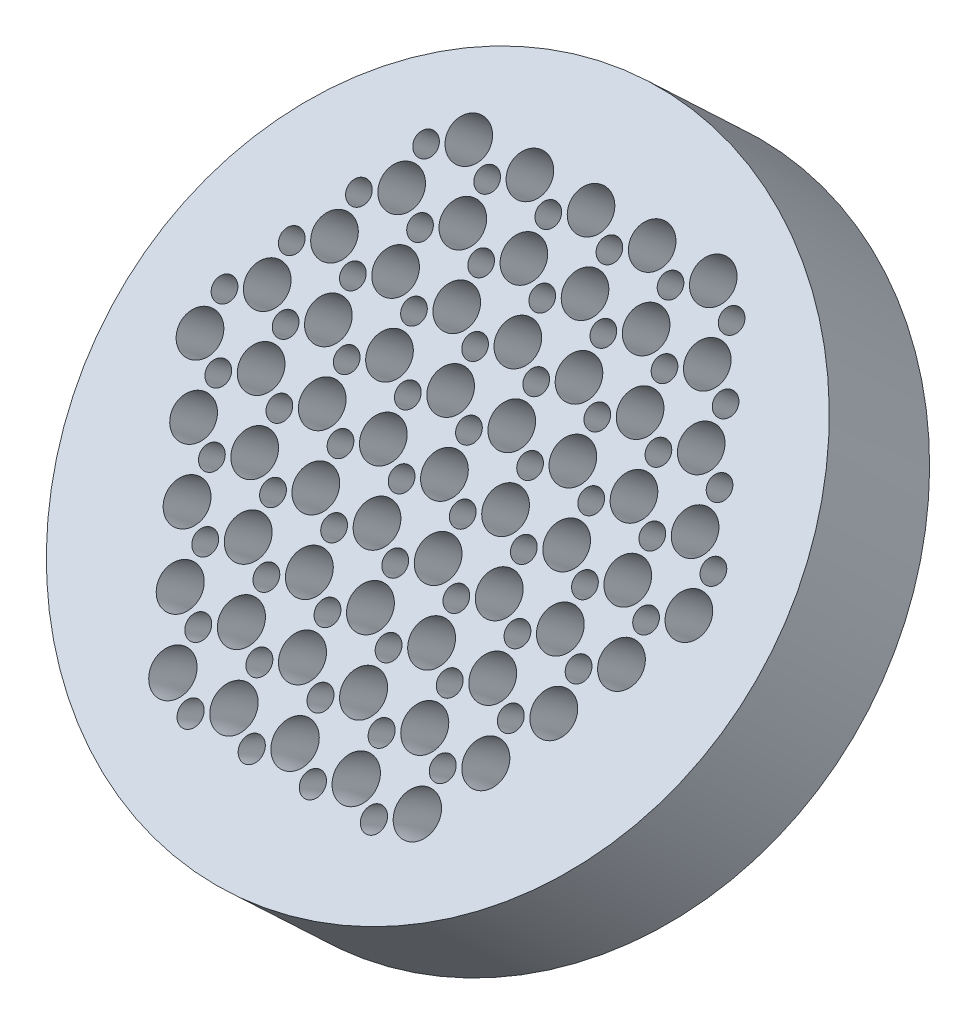
SolidWorks part; units mm, degrees
ref_plane "Спереди" through (0, 0, 0) normal (0, 0, 1) x (1, 0, 0)
ref_plane "Сверху" through (0, 0, 0) normal (0, 1, 0) x (1, 0, 0)
ref_plane "Справа" through (0, 0, 0) normal (1, 0, 0) x (0, 0, -1)
sketch "Sketch1" plane through (0, 0, 0) normal (0, 0, 1) x (1, 0, 0)
  line L0 (3.9, 6.755) -> (7.8, 0) construction
  line L2 (5.85, 10.1325) -> (11.7, 0) construction
  line L4 (7.8, 13.51) -> (15.6, 0) construction
  circle A61 centre (0, 0) radius 18.6468
  circle A131 centre (0, 0) radius 1.25
  circle A484 centre (3.9, 0) radius 1.25
  circle A485 centre (7.8, 0) radius 1.25
  circle A486 centre (11.7, 0) radius 1.25
  circle A487 centre (15.6, 0) radius 1.25
  circle A488 centre (1.95, -3.3775) radius 1.25
  circle A489 centre (3.9, -6.755) radius 1.25
  circle A490 centre (5.85, -10.1325) radius 1.25
  circle A491 centre (7.8, -13.51) radius 1.25
  circle A492 centre (-1.95, -3.3775) radius 1.25
  circle A493 centre (-3.9, -6.755) radius 1.25
  circle A494 centre (-5.85, -10.1325) radius 1.25
  circle A495 centre (-7.8, -13.51) radius 1.25
  circle A496 centre (-3.9, 0) radius 1.25
  circle A497 centre (-7.8, 0) radius 1.25
  circle A498 centre (-11.7, 0) radius 1.25
  circle A499 centre (-15.6, 0) radius 1.25
  circle A500 centre (-1.95, 3.3775) radius 1.25
  circle A501 centre (-3.9, 6.755) radius 1.25
  circle A502 centre (-5.85, 10.1325) radius 1.25
  circle A503 centre (-7.8, 13.51) radius 1.25
  circle A504 centre (1.95, 3.3775) radius 1.25
  circle A505 centre (3.9, 6.755) radius 1.25
  circle A506 centre (5.85, 10.1325) radius 1.25
  circle A507 centre (7.8, 13.51) radius 1.25
  circle A508 centre (5.85, 3.3775) radius 1.25
  circle A509 centre (7.8, 6.755) radius 1.25
  circle A510 centre (9.75, 3.3775) radius 1.25
  circle A511 centre (11.7, 6.755) radius 1.25
  circle A512 centre (9.7491, 10.1341) radius 1.25
  circle A513 centre (13.6509, 3.3759) radius 1.25
  circle A514 centre (5.85, -3.3791) radius 1.25
  circle A515 centre (9.75, -3.3791) radius 1.25
  circle A516 centre (7.8, -6.7566) radius 1.25
  circle A517 centre (11.7, -6.7566) radius 1.25
  circle A518 centre (9.7491, -10.1356) radius 1.25
  circle A519 centre (13.6509, -3.3775) radius 1.25
  circle A520 centre (-0.0013, -6.7573) radius 1.25
  circle A521 centre (1.9487, -10.1348) radius 1.25
  circle A522 centre (-1.9513, -10.1348) radius 1.25
  circle A523 centre (-0.0013, -13.5123) radius 1.25
  circle A524 centre (-3.9032, -13.5123) radius 1.25
  circle A525 centre (3.9005, -13.5123) radius 1.25
  circle A526 centre (-5.8527, -3.3791) radius 1.25
  circle A527 centre (-7.8027, -6.7566) radius 1.25
  circle A528 centre (-9.7527, -3.3791) radius 1.25
  circle A529 centre (-11.7027, -6.7566) radius 1.25
  circle A530 centre (-13.6536, -3.3775) radius 1.25
  circle A531 centre (-9.7518, -10.1356) radius 1.25
  circle A532 centre (-5.8527, 3.3775) radius 1.25
  circle A533 centre (-9.7527, 3.3775) radius 1.25
  circle A534 centre (-7.8027, 6.755) radius 1.25
  circle A535 centre (-11.7027, 6.755) radius 1.25
  circle A536 centre (-9.7518, 10.1341) radius 1.25
  circle A537 centre (-13.6536, 3.3759) radius 1.25
  circle A538 centre (-0.0014, 6.7558) radius 1.25
  circle A539 centre (-1.9514, 10.1333) radius 1.25
  circle A540 centre (1.9486, 10.1333) radius 1.25
  circle A541 centre (-0.0014, 13.5108) radius 1.25
  circle A542 centre (3.9005, 13.5108) radius 1.25
  circle A543 centre (-3.9032, 13.5108) radius 1.25
  circle A544 centre (13.65, -1.1258) radius 2.2517 construction
  circle A545 centre (11.7009, -4.5044) radius 2.2522 construction
  circle A546 centre (9.75, -7.8834) radius 2.2522 construction
  circle A547 centre (7.7987, -11.2591) radius 2.2509 construction
  circle A548 centre (13.65, -1.1258) radius 0.7
  circle A549 centre (11.7009, -4.5044) radius 0.7
  circle A550 centre (9.75, -7.8834) radius 0.7
  circle A551 centre (7.7987, -11.2591) radius 0.7
  circle A552 centre (9.75, -1.1258) radius 0.7
  circle A553 centre (7.8009, -4.5044) radius 0.7
  circle A554 centre (5.85, -7.8834) radius 0.7
  circle A555 centre (3.8987, -11.2591) radius 0.7
  circle A556 centre (5.85, -1.1258) radius 0.7
  circle A557 centre (3.9009, -4.5044) radius 0.7
  circle A558 centre (1.95, -7.8834) radius 0.7
  circle A559 centre (-0.0013, -11.2591) radius 0.7
  circle A560 centre (1.95, -1.1258) radius 0.7
  circle A561 centre (0.0009, -4.5044) radius 0.7
  circle A562 centre (-1.95, -7.8834) radius 0.7
  circle A563 centre (-3.9013, -11.2591) radius 0.7
  circle A564 centre (-1.95, -1.1258) radius 0.7
  circle A565 centre (-3.8991, -4.5044) radius 0.7
  circle A566 centre (-5.85, -7.8834) radius 0.7
  circle A567 centre (-7.8013, -11.2591) radius 0.7
  circle A568 centre (-5.85, -1.1258) radius 0.7
  circle A569 centre (-7.7991, -4.5044) radius 0.7
  circle A570 centre (-9.75, -7.8834) radius 0.7
  circle A572 centre (-9.75, -1.1258) radius 0.7
  circle A573 centre (-11.6991, -4.5044) radius 0.7
  circle A576 centre (-13.65, -1.1258) radius 0.7
  circle A580 centre (-15.5991, -4.5044) radius 0.7 [skipped]
  circle A581 centre (-13.65, -7.8834) radius 0.7 [skipped]
  circle A582 centre (-17.55, -7.8834) radius 0.7 [skipped]
  circle A583 centre (-19.5013, -11.2591) radius 0.7 [skipped]
  circle A584 centre (-15.6013, -11.2591) radius 0.7 [skipped]
  circle A585 centre (-11.7013, -11.2591) radius 0.7 [skipped]
  circle A587 centre (0, 2.2517) radius 2.2517 construction
  circle A588 centre (0, 2.2517) radius 0.7
  circle A589 centre (3.9, 2.2517) radius 0.7
  circle A590 centre (7.8, 2.2517) radius 0.7
  circle A591 centre (11.7, 2.2517) radius 0.7
  circle A592 centre (15.6, 2.2517) radius 0.7
  circle A593 centre (1.9491, 5.6297) radius 2.2522 construction
  circle A594 centre (1.9491, 5.6297) radius 0.7
  circle A595 centre (5.8491, 5.6297) radius 0.7
  circle A596 centre (9.7491, 5.6297) radius 0.7
  circle A597 centre (13.6491, 5.6297) radius 0.7
  circle A598 centre (3.8991, 9.0072) radius 2.2522 construction
  circle A599 centre (3.8991, 9.0072) radius 0.7
  circle A600 centre (7.7991, 9.0072) radius 0.7
  circle A601 centre (11.6991, 9.0072) radius 0.7
  circle A602 centre (5.85, 12.3842) radius 2.2517 construction
  circle A603 centre (5.85, 12.3842) radius 0.7
  circle A604 centre (9.75, 12.3842) radius 0.7
  circle A605 centre (5.85, -14.6358) radius 0.7
  circle A606 centre (1.9509, -14.6353) radius 0.7
  circle A607 centre (-1.9491, -14.6353) radius 0.7
  circle A608 centre (-5.85, -14.6358) radius 0.7
  circle A609 centre (-15.6, 2.2517) radius 0.7
  circle A610 centre (-13.65, 5.6281) radius 0.7
  circle A611 centre (-11.7, 9.0056) radius 0.7
  circle A612 centre (-9.75, 12.3842) radius 0.7
  circle A613 centre (-5.85, 12.3842) radius 0.7
  circle A614 centre (-1.95, 12.3842) radius 0.7
  circle A615 centre (1.95, 12.3842) radius 0.7
  circle A616 centre (-7.8, 9.0056) radius 0.7
  circle A617 centre (-9.75, 5.6281) radius 0.7
  circle A618 centre (-11.7, 2.2517) radius 0.7
  circle A619 centre (-3.9, 9.0056) radius 0.7
  circle A620 centre (-5.85, 5.6281) radius 0.7
  circle A621 centre (-7.8, 2.2517) radius 0.7
  circle A622 centre (0, 9.0056) radius 0.7
  circle A623 centre (-1.95, 5.6281) radius 0.7
  circle A624 centre (-3.9, 2.2517) radius 0.7
  point P51 (0, 0)
  point P125 (-0.0013, -0.0008)
  point P231 (0, 0)
  dimension "D1" = 5
  dimension "D3" = 6
  dimension "D5" = 8
  dimension "D7" = 4
  dimension "D2" = 6
  dimension "D6" = 5
  dimension "D8" = 3
  dimension "D9" = 2
  dimension "D4" = 1.4
  dimension "D10" = 3
sketch "Sketch2" plane through (0, 0, 0) normal (1, 0, 0) x (0, 0, -1)
  line L0 (0, 0) -> (12, 0)
  line L1 (39.4234, -27.4234) -> (39.4234, -34.4234)
  arc A0 (12, 0) -> (39.4234, -27.4234) centre (12, -27.4234) cw
  dimension "D1" = 27.4234
sketch "Sketch4" plane through (0, 0, 0) normal (1, 0, 0) x (0, 0, -1)
  line L1 (-31.2382, 44.0572) -> (87.6543, 44.0572)
  line L2 (-31.2382, 44.0572) -> (-31.2382, -52.5019)
  line L3 (-31.2382, -52.5019) -> (87.6543, -52.5019)
  line L4 (87.6543, 44.0572) -> (87.6543, -52.5019)
sweep "Sweep1" add profiles "Sketch1" path "Sketch2"
sketch "Sketch5" plane through (0, 0, 0) normal (0, 0, 1) x (1, 0, 0)
  circle A0 centre (0, 0) radius 23.5 construction
  circle A1 centre (0, 0) radius 30
  circle A2 centre (0, 0) radius 17.1737
extrude "Boss-Extrude1" add sketch "Sketch5" against normal blind 4
fillet "Fillet1" radius 2 1 edges at (18.6468, 0, -4)
sketch "Sketch6" plane through (0, 0, 0) normal (0, 0, 1) x (1, 0, 0)
  circle A0 centre (0, 0) radius 23.5 construction
  circle A2 centre (23.5, 0) radius 1.75
  circle A4 centre (0, -23.5) radius 1.75
  circle A5 centre (-23.5, 0) radius 1.75
  circle A6 centre (0, 23.5) radius 1.75
  point P14 (0, 0)
  dimension "D1" = 4
extrude "Cut-Extrude2" cut sketch "Sketch6" against normal blind 5
sketch "Sketch8" plane through (0, 0, 0) normal (0, 0, 1) x (1, 0, 0)
  line L0 (0, 0) -> (-19.915, 0)
  line L1 (0, 0) -> (-18.0312, 18.0312) construction
  circle A0 centre (0, 0) radius 25.5 construction
  circle A1 centre (-18.0312, 18.0312) radius 1.75
  circle A2 centre (18.0312, 18.0312) radius 1.75
  circle A3 centre (18.0312, -18.0312) radius 1.75
  circle A4 centre (-18.0312, -18.0312) radius 1.75
  point P15 (0, 0)
  dimension "D1" = 4
extrude "Cut-Extrude3" cut sketch "Sketch8" against normal blind 5 contours A2 | A1 | A4 | A3 region at (-18.0312, 18.0312, 0) region at (18.0312, 18.0312, 0) region at (18.0312, -18.0312, 0) region at (-18.0312, -18.0312, 0)
sketch "Sketch9" plane through (0, 0, 0) normal (1, 0, 0) x (0, 0, -1)
  line L0 (12, -27.4234) -> (45.1688, 7.7454) construction
  line L1 (7.728, -25.3944) -> (14.2754, -31.5694)
  line L2 (7.728, -25.3944) -> (43.7474, 12.797)
  line L3 (14.2754, -31.5694) -> (50.2949, 6.6219)
  line L4 (43.7474, 12.797) -> (50.2949, 6.6219)
  line L5 (32.2851, -12.4737) -> (25.7377, -6.2987) construction
  line L6 (11.0017, -28.4819) -> (47.0212, 9.7095) construction
  line L7 (50.2949, 6.6219) -> (69.9485, -37.822)
  line L8 (69.9485, -37.822) -> (12.1258, -37.822)
  line L9 (12.1258, -37.822) -> (14.2754, -31.5694)
  line L10 (7.728, -25.3944) -> (3.4845, -37.7376)
  line L11 (3.4845, -37.7376) -> (-16.2717, -37.7376)
  line L12 (-16.2717, -37.7376) -> (-16.2717, 41.2638)
  line L13 (-16.2717, 41.2638) -> (52.039, 41.2638)
  line L14 (52.039, 41.2638) -> (43.7474, 12.797)
  point P6 (29.0114, -9.3862)
extrude "Cut-Extrude7" cut sketch "Sketch9" against normal through all both and the other way through all contours L14 L13 L12 L11 L10 L2 | L9 L8 L7 L3 region at (0, 9.6555, -10.0482) region at (0, -22.8974, -43.1441)
sketch "Sketch19" plane through (0, -15.812, -16.7654) normal (0, 0.6861, 0.7275) x (1, 0, 0)
  circle A0 centre (0, 14.7292) radius 1.275 construction
  circle A1 centre (0, 14.7292) radius 17.7695
  circle A2 centre (0, 14.7292) radius 20.7
  circle A3 centre (0, 14.7292) radius 17.7695
  circle A4 centre (0, 14.7292) radius 25.2298
extrude "Boss-Extrude4" add sketch "Sketch19" against normal blind 9 contours A2 A1 region at (-20.1145, -5.0966, -26.8714)
sketch "Sketch20" plane through (0, -15.812, -16.7654) normal (0, 0.6861, 0.7275) x (1, 0, 0)
  circle A0 centre (0, 14.7175) radius 20.6
  circle A1 centre (0, 14.7175) radius 25
extrude "Cut-Extrude12" cut sketch "Sketch20" against normal blind 9
sketch "Sketch21" plane through (0, -21.9871, -23.3128) normal (0, -0.6861, -0.7275) x (-1, 0, 0)
  circle A0 centre (-4.7866, 12.5713) radius 38.0701
  spline S0 degree 3 poles (-5.6605, 10.6323) (-5.341, 10.7271) (-5.1921, 10.8071) (-4.9384, 11.0157) (-4.8312, 11.1467) (-4.6756, 11.4365) (-4.6257, 11.5974) (-4.5897, 11.9256) (-4.6032, 12.0922) (-4.693, 12.4121) (-4.7682, 12.5613) (-4.9209, 12.7575) (-4.9775, 12.8171) (-5.1021, 12.9249) (-5.1707, 12.9733) (-5.3858, 13.0949) (-5.5468, 13.1473) (-5.8732, 13.1847) (-6.0419, 13.17) (-6.2786, 13.0999) (-6.3564, 13.0681) (-6.5019, 12.9908) (-6.5703, 12.9453) (-6.7621, 12.7881) (-6.868, 12.6593) (-7.0256, 12.3661) (-7.0746, 12.2071) (-7.1103, 11.8777) (-7.0963, 11.7106) (-7.0069, 11.3932) (-6.931, 11.2424) (-6.7293, 10.9826) (-6.6016, 10.8715) (-6.3156, 10.709) (-6.1553, 10.6561) (-5.8271, 10.618) (-5.6605, 10.6323) (-5.341, 10.7271) (-5.1921, 10.8071) knots -0.0625 -0.0625 0 0 0.0625 0.0625 0.125 0.125 0.1875 0.1875 0.25 0.25 0.3125 0.3125 0.34375 0.34375 0.375 0.375 0.4375 0.4375 0.5 0.5 0.53125 0.53125 0.5625 0.5625 0.625 0.625 0.6875 0.6875 0.75 0.75 0.8125 0.8125 0.875 0.875 0.9375 0.9375 1 1 1.0625 1.0625 1.125 only from (-5.5008, 10.6797) to (-5.5008, 10.6797) construction
extrude "Cut-Extrude13" cut sketch "Sketch21" against normal blind 0.2
